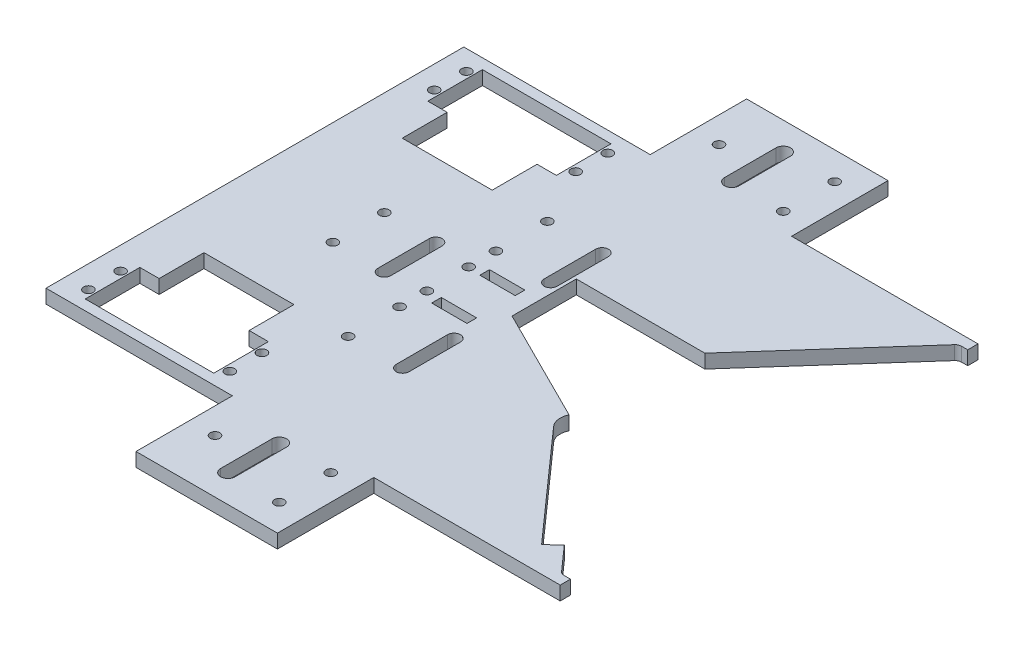
SolidWorks part; units mm, degrees
ref_plane "Front Plane" through (0, 0, 0) normal (0, 0, 1) x (1, 0, 0)
ref_plane "Top Plane" through (0, 0, 0) normal (0, 1, 0) x (1, 0, 0)
ref_plane "Right Plane" through (0, 0, 0) normal (1, 0, 0) x (0, 0, -1)
sketch "Sketch2" plane through (0, 0, 0) normal (0, 1, 0) x (1, 0, 0)
  line L2 (0, 0) -> (0, 65)
  line L3 (0, 65) -> (58, 65)
  line L4 (160, 0) -> (160, 65)
  line L8 (0, 0) -> (160, 0)
  line L9 (102, 65) -> (160, 65)
  line L11 (102, 65) -> (102, 95)
  line L12 (58, 65) -> (58, 95)
  line L13 (58, 95) -> (102, 95)
  dimension "D1" = 65
  dimension "D2" = 160
  dimension "D3" = 44
  dimension "D4" = 30
extrude "Boss-Extrude1" add sketch "Sketch2" along normal blind 4.3
mirror "Mirror1" about plane through (0, 4.3, 0) normal (0, 0, -1) of bodies 101
sketch "Sketch3" plane through (0, 4.3, 0) normal (0, 1, 0) x (1, 0, 0)
  line L0 (160, 61.8) -> (160, -61.8)
  line L1 (120.0126, 20) -> (157.1565, 61.8)
  line L3 (80.0126, 0) -> (80.0126, 20)
  line L4 (80.0126, 20) -> (120.0126, 20)
  line L12 (160, 65) -> (102, 65)
  line L13 (102, 65) -> (102, 95)
  line L15 (102, 95) -> (58, 95)
  line L16 (58, 65) -> (0, 65)
  line L17 (0, 65) -> (0, -65)
  line L18 (0, -65) -> (58, -65)
  line L20 (58, 95) -> (58, 65)
  line L22 (102, -65) -> (160, -65)
  line L23 (160, -65) -> (160, 65)
  line L36 (58, -65) -> (58, -95)
  line L38 (58, -95) -> (102, -95)
  line L39 (58, -95) -> (102, -95)
  line L40 (102, -95) -> (102, -65)
  line L42 (160, -61.8) -> (157.1556, -61.8)
  line L45 (160, 61.8) -> (157.1565, 61.8)
  line L48 (80.0126, 0) -> (120, -20)
  line L49 (120, -20) -> (157.1556, -61.8)
  line M24 (160, -65) -> (160, 65)
  dimension "D2" = 130
  dimension "D3" = 20
  dimension "D4" = 40
  dimension "D1" = 0
extrude "Cut-Extrude1" cut sketch "Sketch3" against normal blind 4.5 contours L48 L49 L1 L4 L3 M24 region at (132.7054, 4.3, -1.1594)
fillet "Fillet1" radius 2 2 edges at (157.1565, 2.15, -61.8) (157.1556, 2.15, 61.8)
ref_axis "Axis1" through (80, 4.3, 95) along (0, 0, -1)
sketch "Sketch4" plane through (0, 4.3, 0) normal (0, 1, 0) x (1, 0, 0)
  line L0 (80, -95) -> (80, 95)
  line L1 (102, -95) -> (58, -95) construction
  line L2 (102, 95) -> (58, 95) construction
ref_plane "Plane2" through (0, 4.3, 0) normal (0, 1, 0) x (1, 0, 0)
sketch "Sketch6" plane through (0, 4.3, 0) normal (0, 1, 0) x (1, 0, 0)
  line L3 (9, -61.8) -> (49, -61.8)
  line L6 (29, -45.8) -> (29, -44.8)
  line L7 (9, -44.8) -> (15, -44.8)
  line L11 (43, -44.8) -> (43, -30.8418)
  line L12 (15, -44.8) -> (15, -30.8418)
  line L13 (15, -30.8418) -> (43, -30.8418)
  line L15 (0, 0) -> (80.0126, 0)
  line L16 (80.0126, 0) -> (120, -20) construction
  line L18 (9, 44.8) -> (15, 44.8)
  line L20 (15, 30.8418) -> (43, 30.8418)
  line L21 (15, 44.8) -> (15, 30.8418)
  line L22 (43, 44.8) -> (43, 30.8418)
  line L25 (15, -45.8) -> (15, -30.8418) construction
  line L27 (9, 61.8) -> (49, 61.8)
  line L30 (4, -61.8) -> (3, -61.8)
  line L31 (0, -61.8) -> (160, -61.8) construction
  line L32 (3, -61.8) -> (4, -61.8)
  line L33 (3, -44.8) -> (3, -62.8) construction
  line L34 (3, -62.8) -> (55, -62.8) construction
  line L35 (55, -44.8) -> (55, -62.8) construction
  line L36 (4, -61.8) -> (54, -61.8) construction
  line L37 (0, 61.8) -> (160, 61.8) construction
  line L38 (54, 61.8) -> (55, 61.8)
  line L39 (54, 61.8) -> (55, 61.8)
  line L40 (43, 44.8) -> (49, 44.8)
  line L41 (4, -45.8) -> (4, -61.8) construction
  line L42 (4, -45.8) -> (54, -45.8) construction
  line L43 (43, -44.8) -> (49, -44.8)
  line L44 (3, -44.8) -> (55, -44.8) construction
  line L45 (29, -45.8) -> (29, -30.8418) construction
  line L46 (43, -45.8) -> (43, -30.8418) construction
  line L47 (54, -45.8) -> (54, -61.8) construction
  line L48 (9, -61.8) -> (49, -61.8)
  line L52 (9, 61.8) -> (9, 44.8)
  line L53 (55, 61.8) -> (54, 61.8)
  line L56 (49, 61.8) -> (49, 44.8)
  line L59 (3, -61.8) -> (4, -61.8)
  line L60 (9, -44.8) -> (9, -61.8)
  line L64 (49, -44.8) -> (49, -61.8)
  dimension "D4" = 1
  dimension "D5" = 14
  dimension "D6" = 14
extrude "Cut-Extrude2" cut sketch "Sketch6" against normal blind 10
sketch "Sketch8" plane through (0, 4.3, 0) normal (0, 1, 0) x (1, 0, 0)
  circle A0 centre (7, 58.8) radius 1.5
  circle A1 centre (7, 48.8) radius 1.5
  circle A2 centre (51, 48.8) radius 1.5
  circle A3 centre (51, 58.8) radius 1.5
  circle A4 centre (7, -48.8) radius 1.5
  circle A5 centre (7, -58.8) radius 1.5
  circle A6 centre (51, -58.8) radius 1.5
  circle A7 centre (51, -48.8) radius 1.5
  dimension "D7" = 3
extrude "Cut-Extrude3" cut sketch "Sketch8" against normal blind 10
sketch "Sketch9" plane through (0, 0, 0) normal (0, -1, 0) x (1, 0, 0)
  line L0 (75.75, 70.4) -> (75.75, 86.4)
  line L1 (75.75, -86.4) -> (75.75, -70.4)
  line L2 (80.25, -86.4) -> (80.25, -70.4)
  line L4 (80.25, 70.4) -> (80.25, 86.4)
  circle A0 centre (94, 70.4) radius 1.5
  circle A1 centre (66, 78.4) radius 1.5
  circle A2 centre (66, -78.4) radius 1.5
  circle A3 centre (94, -86.4) radius 1.5
  circle A4 centre (94, 86.4) radius 1.5
  circle A5 centre (94, -70.4) radius 1.5
  arc A6 (75.75, -86.4) -> (80.25, -86.4) centre (78, -86.4) ccw
  arc A7 (80.25, -70.4) -> (75.75, -70.4) centre (78, -70.4) ccw
  arc A10 (75.75, 70.4) -> (80.25, 70.4) centre (78, 70.4) ccw
  arc A12 (80.25, 86.4) -> (75.75, 86.4) centre (78, 86.4) ccw
  dimension "D1" = 3
extrude "Cut-Extrude4" cut sketch "Sketch9" against normal blind 10
sketch "Sketch7" plane through (0, 4.3, 0) normal (0, 1, 0) x (1, 0, 0)
  line L0 (0, 0) -> (80.0126, 0)
  line L1 (0, 65) -> (0, -65) construction
  line L2 (80.0126, 0) -> (80.0126, 20) construction
  line L3 (80, -95) -> (80, 95) construction
  line L4 (64, -9) -> (75, -9)
  line L5 (64, -6) -> (75, -6)
  line L6 (64, -9) -> (64, -6)
  line L7 (75, -9) -> (75, -6)
  line L8 (64, -7.5) -> (75, -7.5)
  line L9 (64, 7.5) -> (75, 7.5)
  line L10 (75, 9) -> (75, 6)
  line L11 (64, 9) -> (64, 6)
  line L12 (64, 6) -> (75, 6)
  line L13 (64, 9) -> (75, 9)
  circle A0 centre (60.0126, -6.5) radius 1.5
  circle A1 centre (60.0126, 6.5) radius 1.5
  dimension "D1" = 3
  dimension "D2" = 6.5
  dimension "D3" = 20
  dimension "D6" = 11
  dimension "D4" = 5
  dimension "D5" = 3
  dimension "D7" = 7.5
sketch "Sketch10" plane through (0, 4.3, 0) normal (0, 1, 0) x (1, 0, 0)
  line L0 (120, -20) -> (156.5589, -61.1287) construction
  line L1 (123.3218, -23.737) -> (149.8964, -53.6334)
  line L2 (116.263, -23.3218) -> (146.1593, -56.9552)
  line L3 (149.8964, -53.6334) -> (146.1593, -56.9552)
  line L4 (120, -20) -> (156.5589, -61.1287) construction
  line L5 (116.263, -23.3218) -> (152.8218, -64.4505) construction
  arc A0 (123.3218, -23.737) -> (116.263, -23.3218) centre (120, -20) ccw
  dimension "D1" = 5
  dimension "D2" = 45
extrude "Cut-Extrude5" cut sketch "Sketch10" against normal blind 10
sketch "Sketch11" plane through (0, 0, 0) normal (0, -1, 0) x (1, 0, 0)
  line L0 (0, 0) -> (80.0126, 0) construction
  line L1 (80, 95) -> (80, -95) construction
  line L2 (80.0126, 0) -> (0, 0)
  line L4 (75, 31.0313) -> (75, 15.0313)
  line L6 (79, 31.0313) -> (79, 15.0313)
  line L7 (79, -31.0313) -> (79, -15.0313)
  line L8 (75, -31.0313) -> (75, -15.0313)
  circle A0 centre (60, 31) radius 1.5
  circle A1 centre (60, 15) radius 1.5
  arc A2 (75, 31.0313) -> (79, 31.0313) centre (77, 31.0313) cw
  arc A3 (75, 15.0313) -> (79, 15.0313) centre (77, 15.0313) ccw
  arc A4 (75, -15.0313) -> (79, -15.0313) centre (77, -15.0313) cw
  arc A5 (75, -31.0313) -> (79, -31.0313) centre (77, -31.0313) ccw
  circle A6 centre (60, -15) radius 1.5
  circle A7 centre (60, -31) radius 1.5
  point P27 (0, 0)
  point P28 (0, 0)
  point P29 (0, 0)
  dimension "D1" = 3
  dimension "D2" = 16
  dimension "D3" = 15
  dimension "D4" = 20
  dimension "D5" = 15
  dimension "D6" = 4
extrude "Cut-Extrude6" cut sketch "Sketch11" against normal blind 10 contours L4 A3 L6 A2 | L8 A5 L7 A4 | A7 | A0 | A1 | A6 region at (77, 0, 23.0313) region at (77, 0, -23.0313) region at (60, 0, -31)
sketch "Sketch12" plane through (0, 0, 0) normal (0, -1, 0) x (-1, 0, 0)
  line L0 (0, 0) -> (-80.0126, 0) construction
  line L3 (-50.2627, -8) -> (-50.2627, 8)
  line L4 (-50.2627, 0) -> (-46.2627, 0)
  line L5 (-46.2627, -8) -> (-46.2627, 8)
  circle A0 centre (-32.2627, -8) radius 1.5
  circle A1 centre (-32.2627, 8) radius 1.5
  arc A2 (-46.2627, 8) -> (-50.2627, 8) centre (-48.2627, 8) ccw
  arc A3 (-50.2627, -8) -> (-46.2627, -8) centre (-48.2627, -8) ccw
  dimension "D1" = 3
  dimension "D2" = 8
  dimension "D3" = 14
  dimension "D4" = 4
extrude "Cut-Extrude7" cut sketch "Sketch12" against normal blind 10 contours A3 L5 L4 L3 | L4 L5 A2 L3 | A0 | A1 region at (48.2627, 0, 4.7958) region at (48.2627, 0, -4.7958) region at (32.2627, 0, 8) region at (32.2627, 0, -8)
extrude "Cut-Extrude8" cut sketch "Sketch7" against normal blind 9 contours A0 | L4 L7 L5 L6 | L12 L10 L13 L11 | A1
